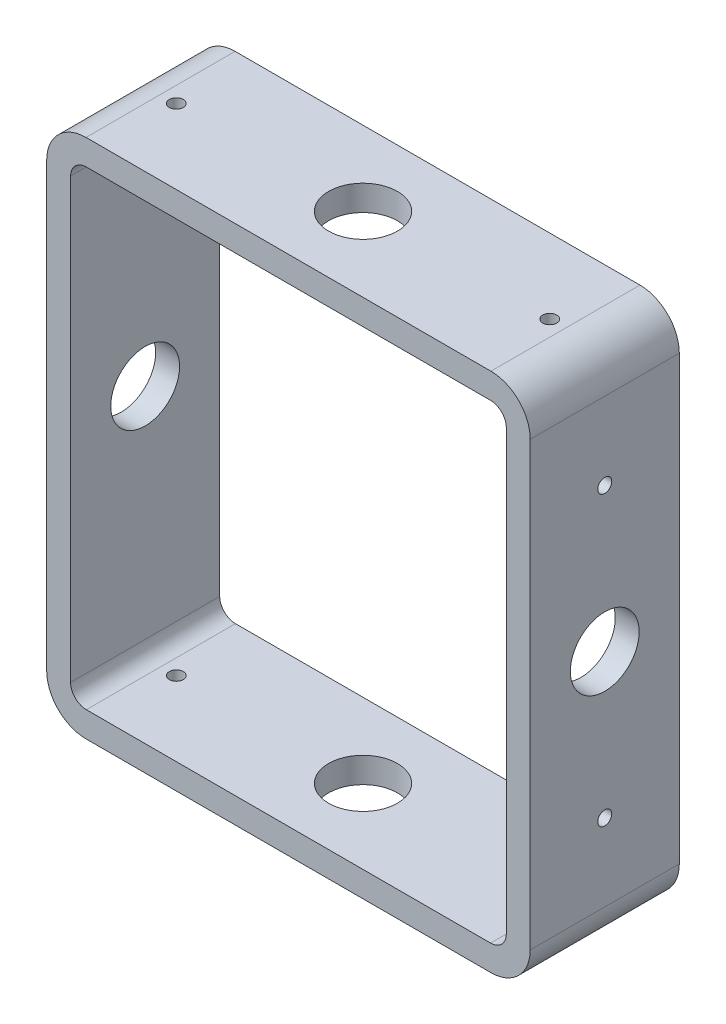
SolidWorks part; units mm, degrees
ref_plane "Front Plane" through (0, 0, 0) normal (0, 0, 1) x (1, 0, 0)
ref_plane "Top Plane" through (0, 0, 0) normal (0, 1, 0) x (1, 0, 0)
ref_plane "Right Plane" through (0, 0, 0) normal (1, 0, 0) x (0, 0, -1)
sketch "Sketch2" plane through (0, 0, 0) normal (0, 0, 1) x (1, 0, 0)
  line L1 (-39.0271, -42.0433) -> (39.0271, -42.0433)
  line L2 (-39.0271, -42.0433) -> (-39.0271, 42.0433)
  line L3 (-39.0271, 42.0433) -> (39.0271, 42.0433)
  line L4 (39.0271, -42.0433) -> (39.0271, 42.0433)
  line L5 (-39.0271, -42.0433) -> (39.0271, 42.0433) construction
  line L6 (-39.0271, 42.0433) -> (39.0271, -42.0433) construction
  line L7 (-35.1663, -37.9349) -> (35.1663, -37.9349)
  line L8 (-35.1663, -37.9349) -> (-35.1663, 37.9349)
  line L9 (-35.1663, 37.9349) -> (35.1663, 37.9349)
  line L10 (35.1663, -37.9349) -> (35.1663, 37.9349)
  line L11 (-35.1663, -37.9349) -> (35.1663, 37.9349) construction
  line L12 (-35.1663, 37.9349) -> (35.1663, -37.9349) construction
  point P0 (0, 0)
  point P6 (0, 0)
  dimension "D1" = 78.0542
  dimension "D2" = 84.0867
  dimension "D3" = 70.3326
  dimension "D4" = 75.8698
extrude "Boss-Extrude1" add sketch "Sketch2" along normal blind 24.0665
sketch "Sketch4" plane through (-39.0271, 0, 0) normal (-1, 0, 0) x (0, 0, 1)
  line L0 (24.0665, 42.0433) -> (0, 42.0433) construction
  line L1 (13.2366, 0) -> (-13.2366, 0) construction
  point P0 (12.0333, 0)
  point P3 (12.0333, 42.0433)
hole_wizard "7/16 (0.4375) Diameter Hole1" positions "Sketch5" profile "Sketch6" hole size "7/16" standard "ANSI Inch" end condition through all
sketch "Sketch5" plane through (-39.0271, 0, 0) normal (-1, 0, 0) x (0, 0, 1)
  point P0 (12.0333, 0)
sketch "Sketch6" plane through (-39.0271, 0, 12.0333) normal (0, 1, 0) x (0, 0, 1)
  line L0 (0, 0) -> (0, 78.0542)
  line L1 (0, 78.0542) -> (5.5562, 78.0542)
  line L2 (5.5562, 78.0542) -> (5.5562, 0)
  line L5 (5.5562, 0) -> (0, 0)
  line L11 (0, -6.35) -> (0, 107.95) construction
  dimension "Thru Hole Dia." = 11.1125
  dimension "Thru Hole Depth" = 78.0542
sketch "Sketch8" plane through (0, 42.0433, 0) normal (0, 1, 0) x (1, 0, 0)
  line L0 (39.0271, -24.0665) -> (39.0271, 0) construction
  line L1 (0, -13.2366) -> (0, 13.2366) construction
  point P0 (0, -12.0333)
  point P3 (39.0271, -12.0333)
hole_wizard "7/16 (0.4375) Diameter Hole2" positions "Sketch9" profile "Sketch10" hole size "7/16" standard "ANSI Inch" end condition through all
sketch "Sketch9" plane through (0, 42.0433, 0) normal (0, 1, 0) x (1, 0, 0)
  point P0 (0, -12.0333)
sketch "Sketch10" plane through (0, 42.0433, 12.0333) normal (1, 0, 0) x (0, 0, 1)
  line L0 (0, 0) -> (0, 84.0867)
  line L1 (0, 84.0867) -> (5.5562, 84.0867)
  line L2 (5.5562, 84.0867) -> (5.5562, 0)
  line L5 (5.5562, 0) -> (0, 0)
  line L11 (0, -6.35) -> (0, 107.95) construction
  dimension "Thru Hole Dia." = 11.1125
  dimension "Thru Hole Depth" = 84.0867
fillet "Fillet2" radius 6.35 4 edges at (39.0271, -42.0433, 12.0333) (-39.0271, -42.0433, 12.0333) (39.0271, 42.0433, 12.0333) (-39.0271, 42.0433, 12.0333)
fillet "Fillet3" radius 2.54 4 edges at (-35.1663, -37.9349, 12.0333) (-35.1663, 37.9349, 12.0333) (35.1663, -37.9349, 12.0333) (35.1663, 37.9349, 12.0333)
sketch "Sketch11" plane through (39.0271, 0, 0) normal (1, 0, 0) x (0, 0, -1)
  line L0 (-12.0333, 23.241) -> (-12.0333, -23.241) construction
  line L1 (13.2366, 0) -> (-13.2366, 0) construction
  point P0 (-12.0333, 23.241)
  point P1 (-12.0333, -23.241)
  point P7 (-12.0333, 0)
  dimension "D1" = 46.482
hole_wizard "#4-40 Tapped Hole1" positions "Sketch12" profile "Sketch13" tap size "#4-40" standard "ANSI Inch" end condition up to next
sketch "Sketch12" plane through (39.0271, 0, 0) normal (1, 0, 0) x (0, 0, -1)
  point P0 (-12.0333, 23.241)
  point P3 (-12.0333, -23.241)
sketch "Sketch13" plane through (39.0271, 23.241, 12.0333) normal (0, 1, 0) x (0, 0, -1)
  line L0 (0, 0) -> (0, 3.8608)
  line L1 (0, 3.8608) -> (1.1303, 3.8608)
  line L2 (1.1303, 3.8608) -> (1.1303, 0)
  line L5 (1.1303, 0) -> (0, 0)
  line L11 (0, -6.35) -> (0, 107.95) construction
  dimension "Thru Tap Drill Dia." = 2.2606
  dimension "Thru Tap Drill Depth" = 3.8608
cosmetic thread "Hole Thread1" parameters "D2"=2.8448
cosmetic thread "Hole Thread2" parameters "D2"=2.8448
sketch "Sketch14" plane through (0, -42.0433, 0) normal (0, -1, 0) x (1, 0, 0)
  line L0 (32.6771, 12.0333) -> (-32.6771, 12.0333) construction
  line L1 (32.6771, 0) -> (32.6771, 24.0665) construction
  line L2 (-32.6771, 24.0665) -> (-32.6771, 0) construction
  point P6 (30.1371, 12.0333)
  point P7 (-30.1371, 12.0332)
  dimension "D1" = 2.54
  dimension "D2" = 2.54
hole_wizard "#4-40 Tapped Hole2" positions "Sketch15" profile "Sketch17" tap size "#4-40" standard "ANSI Inch" end condition through all
sketch "Sketch15" plane through (0, -42.0433, 0) normal (0, -1, 0) x (-1, 0, 0)
  point P0 (-30.1371, -12.0333)
  point P3 (30.1371, -12.0332)
sketch "Sketch17" plane through (30.1371, -42.0433, 12.0333) normal (1, 0, 0) x (0, 0, -1)
  line L0 (0, 0) -> (0, 84.0867)
  line L1 (0, 84.0867) -> (1.1303, 84.0867)
  line L2 (1.1303, 84.0867) -> (1.1303, 0)
  line L5 (1.1303, 0) -> (0, 0)
  line L11 (0, -6.35) -> (0, 107.95) construction
  dimension "Thru Tap Drill Dia." = 2.2606
  dimension "Thru Tap Drill Depth" = 84.0867
cosmetic thread "Hole Thread3" parameters "D2"=2.8448
cosmetic thread "Hole Thread4" parameters "D2"=2.8448
